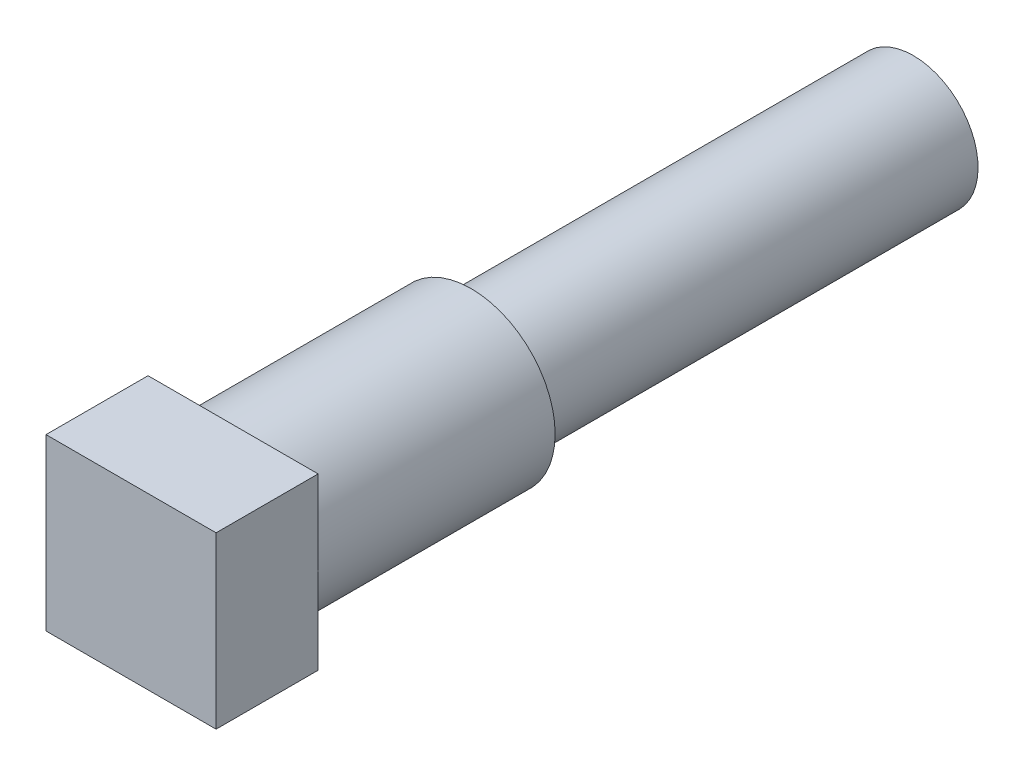
SolidWorks part; units mm, degrees
material "Alloy Steel (SS)"
ref_plane "Front Plane" through (0, 0, 0) normal (0, 0, 1) x (1, 0, 0)
ref_plane "Top Plane" through (0, 0, 0) normal (0, 1, 0) x (1, 0, 0)
ref_plane "Right Plane" through (0, 0, 0) normal (1, 0, 0) x (0, 0, -1)
sketch "Sketch1" plane through (0, 0, 0) normal (1, 0, 0) x (0, 0, -1)
  line L0 (4.8921, 0) -> (44.3738, 0)
  line L1 (0, 3.194) -> (0, 4.064)
  line L2 (6.2738, 3.3115) -> (6.2738, 4.445)
  line L3 (0.635, 4.699) -> (6.0198, 4.699)
  line L4 (-1000, 4.699) -> (49000, 4.699) construction
  line L5 (-1000, 0) -> (49000, 0) construction
  line L6 (44.3738, 0) -> (44.3738, 2.159)
  line L7 (0, -1000) -> (0, 49000) construction
  line L8 (6.2738, -1000) -> (6.2738, 49000) construction
  line L9 (44.3738, -1000) -> (44.3738, 49000) construction
  line L10 (0, 3.194) -> (0, 0)
  line L11 (0, 0) -> (4.8921, 0)
  line L15 (25.3238, 3.1236) -> (43.4092, 3.1236)
  line L17 (4.8921, 3.1236) -> (44.3738, 3.1236) construction
  line L18 (6.2738, 3.3115) -> (6.2738, 3.1337)
  line L19 (18.9738, 3.1337) -> (25.3238, 3.1236)
  line L20 (6.2738, 3.1337) -> (6.4516, 3.1337)
  line L21 (43.4092, 3.1236) -> (44.3738, 2.159)
  line L22 (6.4516, 3.1337) -> (18.9738, 3.1337)
  line L23 (4.8921, 3.1337) -> (44.3738, 3.1337) construction
  line L24 (6.0198, 4.699) -> (6.2738, 4.699)
  line L25 (6.2738, 4.699) -> (6.2738, 4.445)
  line L26 (0, 4.064) -> (0, 4.699)
  line L27 (0, 4.699) -> (0.635, 4.699)
  point P9 (0, 4.699)
  point P13 (6.2738, 4.699)
  dimension "D1" = 6.2738
  dimension "D2" = 4.699
  dimension "D10" = 3.1337
  dimension "D12" = 6.35
  dimension "D13" = 19.05
  dimension "D14" = 45
  dimension "D15" = 3.1236
  dimension "D16" = 0.9646
  dimension "D17" = 0.092
  dimension "D5" = 0.635
  dimension "D7" = 0.254
revolve "Revolve1" add sketch "Sketch1" angle 360 about L0
sketch "Sketch3" plane through (0, 0, -44.3738) normal (0, 0, -1) x (-1, 0, 0)
  circle A0 centre (0, 0) radius 3.1337
  circle A1 centre (0, 0) radius 2.159 construction
  dimension "D1" = 6.2674
curve "Helix/Spiral1" pitch 1.27 height 38.1 turns 30
sketch "Sketch4" plane through (0, 0, 0) normal (1, 0, 0) x (0, 0, -1)
  line L0 (44.3738, 3.1236) -> (44.5325, 3.1236) construction
  line L1 (45.207, 2.3669) -> (45.0882, 2.1612) construction
  line L2 (44.3738, 3.1236) -> (44.4532, 3.261) construction
  line L3 (44.9294, 2.4362) -> (45.2469, 2.4362) construction
  line L4 (44.4532, 3.261) -> (44.5325, 3.1236) construction
  line L5 (45.0882, 2.1612) -> (44.9694, 2.3669) construction
  line L6 (44.5118, 3.1594) -> (44.9694, 2.3669)
  line L7 (45.207, 2.3669) -> (45.6645, 3.1594)
  line L8 (44.5118, 3.1594) -> (45.6645, 3.1594)
  line L9 (44.3738, 2.159) -> (44.3738, -2.159) construction
  arc A0 (44.9694, 2.3669) -> (45.207, 2.3669) centre (45.0882, 2.4355) ccw
  dimension "D9" = 0.1372
  dimension "D2" = 1.0999
  dimension "D5" = 0.275
  dimension "D6" = 1.1527
  dimension "D7" = 0.7144
  dimension "D10" = 0.7233
  dimension "D11" = 0.0692
  dimension "D13" = 0.1587
  dimension "D3" = 0.1375
  dimension "D4" = 0.3175
  dimension "D8" = 60
sweep "Cut-Sweep1" [suppressed] cut profiles "Sketch4" path "Helix/Spiral1"
sketch "Sketch5" [suppressed] plane through (0, 0, 0) normal (1, 0, 0) x (0, 0, -1)
  line L3 (6.4267, 3.1337) -> (6.8694, 2.3669)
  line L4 (7.107, 2.3669) -> (7.5497, 3.1337)
  line L5 (7.5497, 3.1337) -> (6.4267, 3.1337)
  line L6 (6.4267, 3.1337) -> (6.8694, 2.3669)
  line L7 (7.107, 2.3669) -> (7.5497, 3.1337)
  line L8 (7.5497, 3.1337) -> (6.4267, 3.1337)
  arc A1 (6.8694, 2.3669) -> (7.107, 2.3669) centre (6.9882, 2.4355) ccw
  arc A2 (6.8694, 2.3669) -> (7.107, 2.3669) centre (6.9882, 2.4355) ccw
  dimension "D1" = 0
extrude "Cut-Extrude2" [suppressed] cut sketch "Sketch5" against normal through all
sketch "Sketch6" plane through (0, 0, -44.3738) normal (0, 0, -1) x (-1, 0, 0)
  circle A0 centre (0, 0) radius 3.6875
extrude "Cut-Extrude3" cut sketch "Sketch6" against normal blind 29.1338
sketch "Sketch7" plane through (0, 0, -15.24) normal (0, 0, -1) x (-1, 0, 0)
  circle A0 centre (0, 0) radius 2.413
  dimension "D1" = 4.826
extrude "Boss-Extrude1" add sketch "Sketch7" along normal blind 16.51 contours A0
sketch "Sketch9" plane through (0, 0, 0) normal (0, 0, 1) x (1, 0, 0)
  circle A0 centre (0, 0) radius 4.699
extrude "Cut-Extrude4" cut sketch "Sketch9" against normal blind 6.35
sketch "Sketch10" plane through (0, 0, -6.35) normal (0, 0, 1) x (1, 0, 0)
  line L1 (-3.175, 3.175) -> (3.175, 3.175)
  line L2 (-3.175, 3.175) -> (-3.175, -3.175)
  line L3 (-3.175, -3.175) -> (3.175, -3.175)
  line L4 (3.175, 3.175) -> (3.175, -3.175)
  line L5 (-3.175, 3.175) -> (3.175, -3.175) construction
  line L6 (-3.175, -3.175) -> (3.175, 3.175) construction
  point P0 (0, 0)
  dimension "D1" = 6.35
  dimension "D2" = 6.35
extrude "Boss-Extrude3" add sketch "Sketch10" along normal blind 3.81
sketch "Stock Rod Diameter" [suppressed] plane through (0, 0, -2.54) normal (0, 0, 1) x (1, 0, 0)
  circle A0 centre (0, 0) radius 4.7625
  dimension "D1" = 9.525
equation "\"P\"= .05in"
equation "\"H\"= \"P\" * cos ( 30deg )"
equation "\"D13@Sketch4\" = .125 * \"P\""
equation "\"D2@Sketch4\" = \"H\""
equation "\"D3@Sketch4\" = .125 * \"H\""
equation "\"D5@Sketch4\" = .25 * \"H\""
equation "\"D4@Sketch4\" = .25 * \"P\""
equation "\"D9@Sketch4\" = .108 * \"P\""
